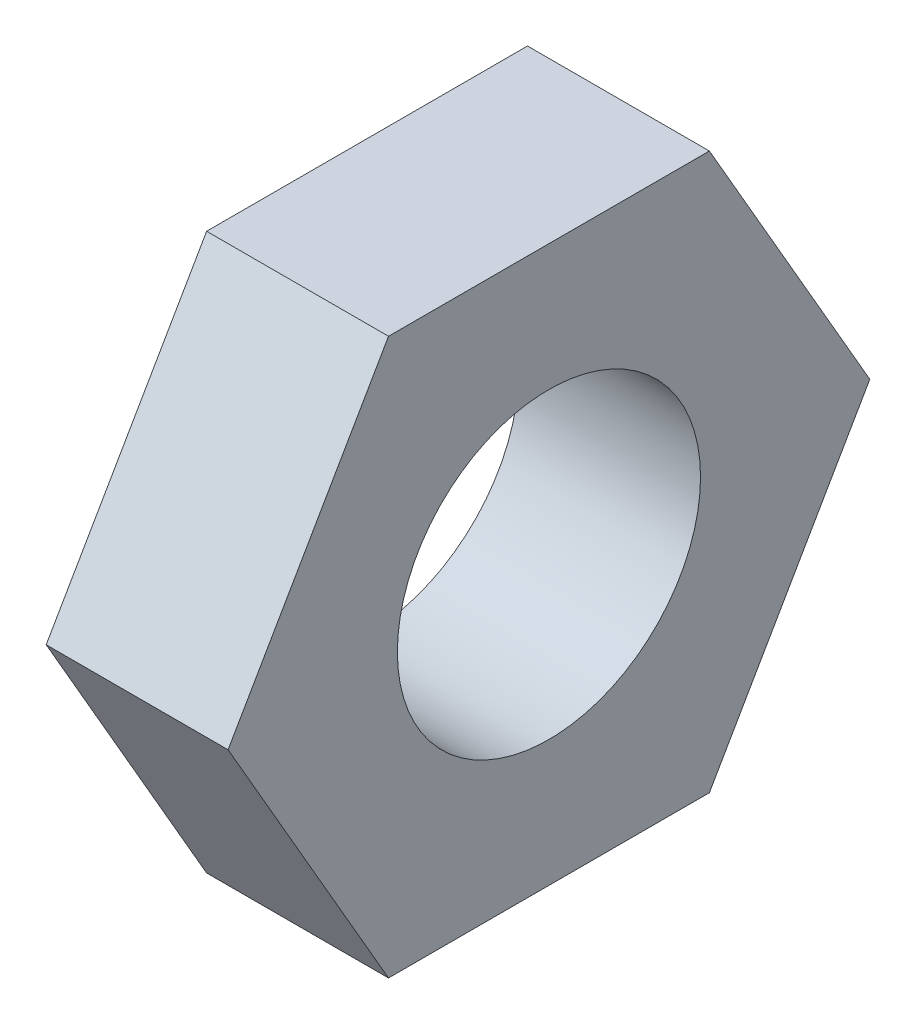
SolidWorks part; units mm, degrees
ref_plane "Front Plane" through (0, 0, 0) normal (0, 0, 1) x (1, 0, 0)
ref_plane "Top Plane" through (0, 0, 0) normal (0, 1, 0) x (1, 0, 0)
ref_plane "Right Plane" through (0, 0, 0) normal (1, 0, 0) x (0, 0, -1)
sketch "Nut Sketch" plane through (0, 0, 0) normal (1, 0, 0) x (0, 0, -1)
  line L0 (3.1754, 0) -> (1.5877, 2.75)
  line L1 (1.5877, 2.75) -> (-1.5877, 2.75)
  line L2 (-1.5877, 2.75) -> (-3.1754, 0)
  line L3 (-3.1754, 0) -> (-1.5877, -2.75)
  line L4 (-1.5877, -2.75) -> (1.5877, -2.75)
  line L5 (1.5877, -2.75) -> (3.1754, 0)
extrude "Nut" add sketch "Nut Sketch" along normal blind 1.8
ref_axis "Engine Axis" through (1.89, 0, 0) along (-1, 0, 0)
sketch "Thread Sketch" plane through (0, 0, 0) normal (0, 0, 1) x (1, 0, 0)
  line L0 (-1000, 0) -> (1000, 0) construction
  line L1 (-1, 0) -> (2.8, 0)
  line L2 (2.8, 0) -> (2.8, 1.5)
  line L3 (2.8, 1.5) -> (-1, 1.5)
  line L4 (-1, 1.5) -> (-1, 0)
revolve "Thread" cut sketch "Thread Sketch" angle 360 about L0
